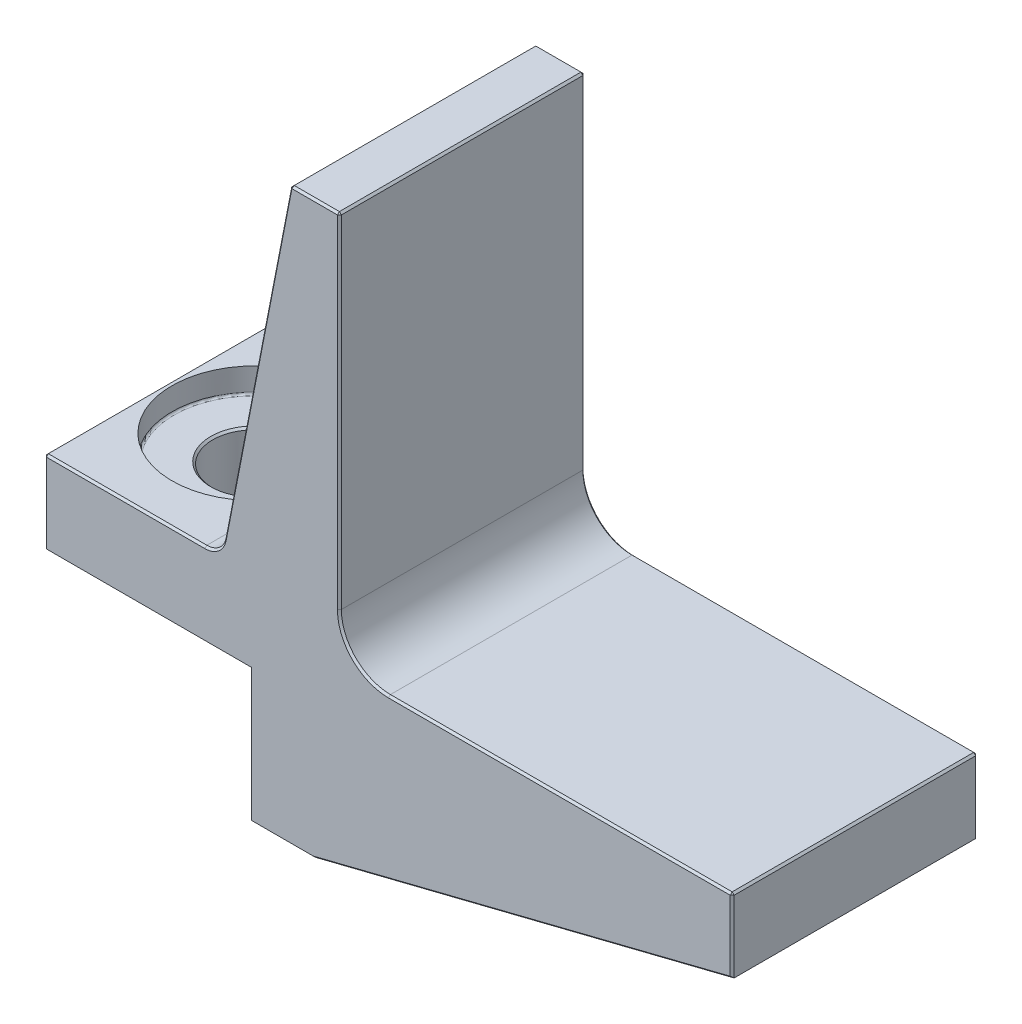
SolidWorks part; units mm, degrees
other "Markup1"
sketch "Sketch7" plane through (-38.1608, 50.8, 31.75) normal (-0.1424, 0.1459, 0.979) x (0.9898, 0.0098, 0.1425)
material "7075-T6 (SN)"
ref_plane "Front Plane" through (0, 0, 0) normal (0, 0, 1) x (1, 0, 0)
ref_plane "Top Plane" through (0, 0, 0) normal (0, 1, 0) x (1, 0, 0)
ref_plane "Right Plane" through (0, 0, 0) normal (1, 0, 0) x (0, 0, -1)
sketch "Sketch1" plane through (0, 0, 0) normal (0, 0, 1) x (1, 0, 0)
  line L0 (0, 0) -> (50.8, 0)
  line L1 (50.8, 0) -> (50.8, -9.525)
  line L2 (-11.6178, -5.9413) -> (-38.1608, -5.9413)
  line L3 (-38.1608, -5.9413) -> (-38.1608, 4.8537)
  line L4 (-38.1608, 4.8537) -> (-15.3008, 4.8537)
  line L5 (-15.3008, 4.8537) -> (-6.35, 50.8)
  line L6 (-6.35, 50.8) -> (0, 50.8)
  line L7 (0, 50.8) -> (0, 0)
  line L8 (-11.6178, -5.9413) -> (-11.6178, -23.0863)
  line L9 (-11.6178, -23.0863) -> (-3.3628, -23.0863)
  line L10 (-3.3628, -23.0863) -> (50.8, -9.525)
  dimension "D1" = 50.8
  dimension "D2" = 50.8
  dimension "D3" = 9.525
  dimension "D4" = 38.1608
  dimension "D5" = 6.35
  dimension "D6" = 22.86
  dimension "D7" = 26.543
  dimension "D8" = 10.795
  dimension "D9" = 17.145
  dimension "D10" = 8.255
  dimension "D11" = 4.8537
extrude "Boss-Extrude1" add sketch "Sketch1" along normal blind 31.75
hole_wizard "CBORE for 3/8 Binding Head Machine Screw1" positions "Sketch6" profile "Sketch3" counterbore size "3/8" standard "ANSI Inch" end condition through all
sketch "Sketch6" plane through (0, 4.8537, 0) normal (0, 1, 0) x (1, 0, 0)
  line L1 (-38.1608, -31.75) -> (-38.1608, 0) construction
  point P0 (-26.8578, -15.875)
  point P8 (-38.1608, -15.875)
  dimension "D1" = 11.303
sketch "Sketch3" plane through (-26.8578, 4.8537, 15.875) normal (1, 0, 0) x (0, 0, 1)
  line L0 (0, 0) -> (0, 27.94)
  line L1 (0, 27.94) -> (5.3975, 27.94)
  line L3 (5.3975, 27.94) -> (5.3975, 3.175)
  line L4 (10.668, 3.175) -> (5.3975, 3.175)
  line L5 (10.668, 3.175) -> (10.668, 0)
  line L7 (10.668, 0) -> (0, 0)
  line L11 (0, 0) -> (0, 107.95) construction
  dimension "Thru Hole Dia." = 10.795
  dimension "Thru Hole Depth" = 27.94
  dimension "C'Bore Depth" = 3.175
fillet "Fillet1" radius 2.54 1 edges at (-15.3008, 4.8537, 15.875)
fillet "Fillet2" radius 6.35 1 edges at (0, 0, 15.875)
chamfer "Chamfer1" distance 0.254 angle 45 31 edges at (-6.35, 50.8, 15.875) (-3.175, 50.8, 0) (-10.6253, 28.854, 0) (-15.7785, 5.4334, 0) (-27.7773, 4.8537, 0) (-38.1608, -0.5438, 0) (-24.8893, -5.9413, 0) (50.8, -4.7625, 0) (28.575, 0, 0) (1.8599, 1.8599, 0) (0, 28.575, 0) (50.8, -4.7625, 31.75) (-24.8893, -5.9413, 31.75) (-38.1608, -5.9413, 15.875) (-38.1608, -0.5438, 31.75) (-38.1608, 4.8537, 15.875) (-27.7773, 4.8537, 31.75) (-15.7785, 5.4334, 31.75) (-10.6253, 28.854, 31.75) (-3.175, 50.8, 31.75) (0, 50.8, 15.875) (0, 28.575, 31.75) (1.8599, 1.8599, 31.75) (28.575, 0, 31.75) (50.8, 0, 15.875) (-11.6178, -14.5138, 0) (-7.4903, -23.0863, 0) (23.7186, -16.3057, 0) (23.7186, -16.3057, 31.75) (-7.4903, -23.0863, 31.75) (-11.6178, -14.5138, 31.75) first distance on face at (-3.175, 50.8, 15.875) first distance on face at (-12.0593, 21.493, 15.6351) first distance on face at (-15.9628, 5.6571, 5.4759) first distance on face at (-27.6714, 4.8537, 15.875) first distance on face at (-38.1608, -0.5438, 15.875) first distance on face at (-32.2553, -5.9413, 15.875) first distance on face at (50.8, -4.7625, 15.875) first distance on face at (-2.6585, 4.2479, 0) first distance on face at (2.5174, 2.5174, 15.875) first distance on face at (0, 28.575, 15.875) first distance on face at (-15.9628, 5.6571, 26.2741) first distance on face at (-2.6585, 4.2479, 31.75) first distance on face at (-11.6178, -14.5138, 15.875) first distance on face at (-7.4903, -23.0863, 15.875) first distance on face at (23.7186, -16.3057, 15.875)
fillet "Fillet3" radius 0.254 1 edges at (-26.8578, 1.6787, 26.543)
chamfer "Chamfer2" distance 0.254 angle 45 1 edges at (-32.2553, -5.9413, 15.875)
chamfer "Chamfer3" distance 0.254 angle 45 1 edges at (-26.8578, 1.6787, 21.2725)
